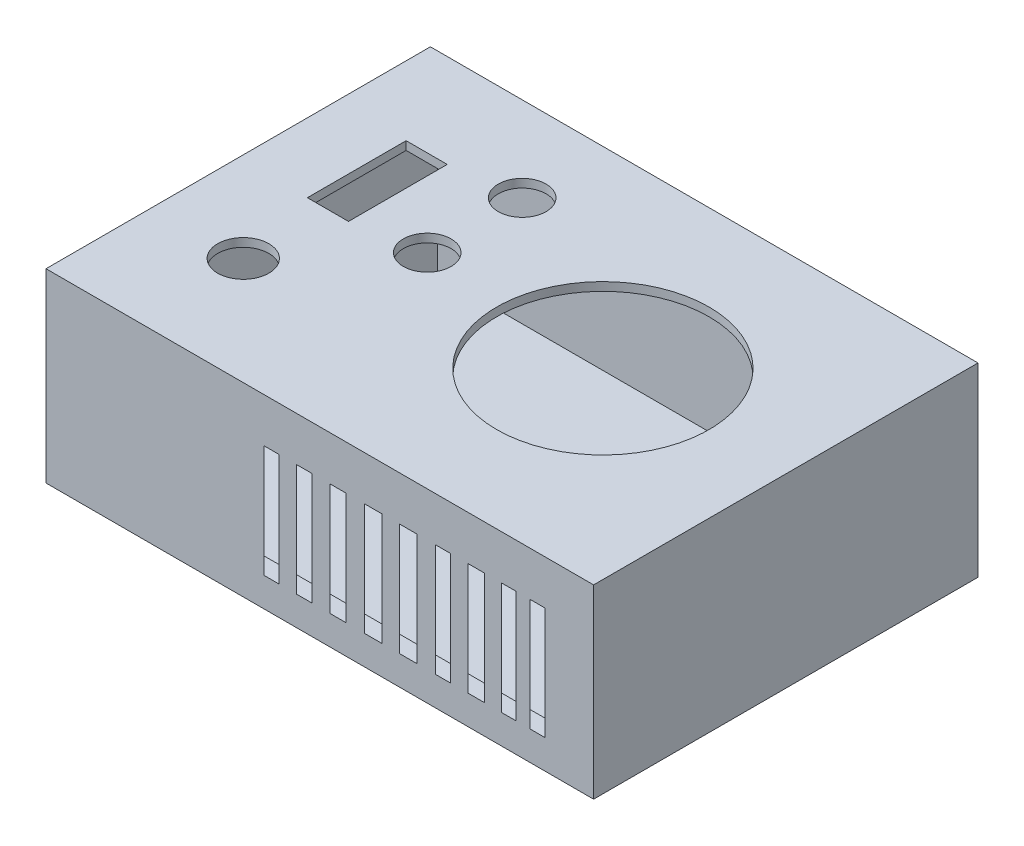
SolidWorks part; units mm, degrees
ref_plane "Front Plane" through (0, 0, 0) normal (0, 0, 1) x (1, 0, 0)
ref_plane "Top Plane" through (0, 0, 0) normal (0, 1, 0) x (1, 0, 0)
ref_plane "Right Plane" through (0, 0, 0) normal (1, 0, 0) x (0, 0, -1)
sketch "Sketch1" plane through (0, 0, 0) normal (0, 1, 0) x (1, 0, 0)
  line L1 (-75.1936, -52.7816) -> (75.1936, -52.7816)
  line L2 (-75.1936, -52.7816) -> (-75.1936, 52.7816)
  line L3 (-75.1936, 52.7816) -> (75.1936, 52.7816)
  line L4 (75.1936, -52.7816) -> (75.1936, 52.7816)
  line L5 (-75.1936, -52.7816) -> (75.1936, 52.7816) construction
  line L6 (-75.1936, 52.7816) -> (75.1936, -52.7816) construction
  line L7 (-82.4227, -57.856) -> (82.4227, -57.856)
  line L8 (-82.4227, -57.856) -> (-82.4227, 57.856)
  line L9 (-82.4227, 57.856) -> (82.4227, 57.856)
  line L10 (82.4227, -57.856) -> (82.4227, 57.856)
  line L11 (-82.4227, -57.856) -> (82.4227, 57.856) construction
  line L12 (-82.4227, 57.856) -> (82.4227, -57.856) construction
  point P0 (0, 0)
  point P6 (0, 0)
  point P11 (75.1936, 52.7816)
  dimension "D1" = 5.0743
extrude "Boss-Extrude1" add sketch "Sketch1" along normal blind 2.54 contours L1 L4 L3 L2 | L7 L10 L9 L8 L4 L1 L2 L3 region at (0, 0, 0) region at (-80.4086, 0, 0)
extrude "Boss-Extrude2" add sketch "Sketch1<3>" along normal blind 53.34
sketch "Sketch1<3>" plane through (0, 0, 0) normal (0, 1, 0) x (1, 0, 0) same geometry as "Sketch1"
extrude "Boss-Extrude3" add sketch "Sketch1<4>" along normal blind 2.54 from surface contours L1 L4 L3 L2 | L7 L10 L9 L8 L4 L1 L2 L3 region at (0, 0, 0) region at (-80.4086, 0, 0) starting at face at (0, 53.34, 0)
sketch "Sketch1<4>" plane through (0, 0, 0) normal (0, 1, 0) x (1, 0, 0) same geometry as "Sketch1"
sketch "Sketch2" plane through (0, 55.88, 0) normal (0, 1, 0) x (1, 0, 0)
  line L1 (-61.5935, 29.7244) -> (-49.2208, 29.7244)
  line L2 (-61.5935, 29.7244) -> (-61.5935, 0)
  line L3 (-61.5935, 0) -> (-49.2208, 0)
  line L4 (-49.2208, 29.7244) -> (-49.2208, 0)
  circle A0 centre (27.3574, 0) radius 31.968
  circle A1 centre (-29.2246, 32.2896) radius 7.1976
  circle A2 centre (-29.2246, 3.7027) radius 7.1976
  circle A3 centre (-55.4071, -25.4896) radius 7.7022
extrude "Cut-Extrude1" cut sketch "Sketch2" against normal blind 2.54
ref_plane "Plane1" through (-12.2833, 0, -12.2833) normal (0.7071, 0, 0.7071) x (0.7071, 0, -0.7071)
sketch "Sketch3" plane through (0, 0, 57.856) normal (0, 0, 1) x (1, 0, 0)
  line L1 (67.7666, 42.5337) -> (63.2943, 42.5337)
  line L2 (67.7666, 42.5337) -> (67.7666, 8.7527)
  line L3 (67.7666, 8.7527) -> (63.2943, 8.7527)
  line L4 (63.2943, 42.5337) -> (63.2943, 8.7527)
  line L5 (59.1008, 42.5337) -> (54.622, 42.5337)
  line L6 (59.1008, 42.5337) -> (59.1008, 8.7527)
  line L7 (59.1008, 8.7527) -> (54.622, 8.7527)
  line L8 (54.622, 42.5337) -> (54.622, 8.7527)
  line L9 (49.6089, 42.5337) -> (44.5946, 42.5337)
  line L10 (49.6089, 42.5337) -> (49.6089, 8.7527)
  line L11 (49.6089, 8.7527) -> (44.5946, 8.7527)
  line L12 (44.5946, 42.5337) -> (44.5946, 8.7527)
  line L13 (39.3073, 42.5337) -> (34.8284, 42.5337)
  line L14 (39.3073, 42.5337) -> (39.3073, 8.7527)
  line L15 (39.3073, 8.7527) -> (34.8284, 8.7527)
  line L16 (34.8284, 42.5337) -> (34.8284, 8.7527)
  line L17 (29.2799, 42.5337) -> (23.9945, 42.5337)
  line L18 (29.2799, 42.5337) -> (29.2799, 8.7527)
  line L19 (29.2799, 8.7527) -> (23.9945, 8.7527)
  line L20 (23.9945, 42.5337) -> (23.9945, 8.7527)
  line L21 (18.7105, 42.5337) -> (13.4219, 42.5337)
  line L22 (18.7105, 42.5337) -> (18.7105, 8.7527)
  line L23 (18.7105, 8.7527) -> (13.4219, 8.7527)
  line L24 (13.4219, 42.5337) -> (13.4219, 8.7527)
  line L25 (7.8733, 42.5337) -> (3.1104, 42.5337)
  line L26 (7.8733, 42.5337) -> (7.8733, 8.7527)
  line L27 (7.8733, 8.7527) -> (3.1104, 8.7527)
  line L28 (3.1104, 42.5337) -> (3.1104, 8.7527)
  line L29 (-2.2943, 42.5337) -> (-6.9976, 42.5337)
  line L30 (-2.2943, 42.5337) -> (-2.2943, 8.7527)
  line L31 (-2.2943, 8.7527) -> (-6.9976, 8.7527)
  line L32 (-6.9976, 42.5337) -> (-6.9976, 8.7527)
  line L33 (-12.3584, 42.5337) -> (-16.8156, 42.5337)
  line L34 (-12.3584, 42.5337) -> (-12.3584, 8.7527)
  line L35 (-12.3584, 8.7527) -> (-16.8156, 8.7527)
  line L36 (-16.8156, 42.5337) -> (-16.8156, 8.7527)
extrude "Cut-Extrude2" cut sketch "Sketch3" along direction (0.7071, 0, 0.7071) on the side against the normal up to next (5.0743 mm away)
